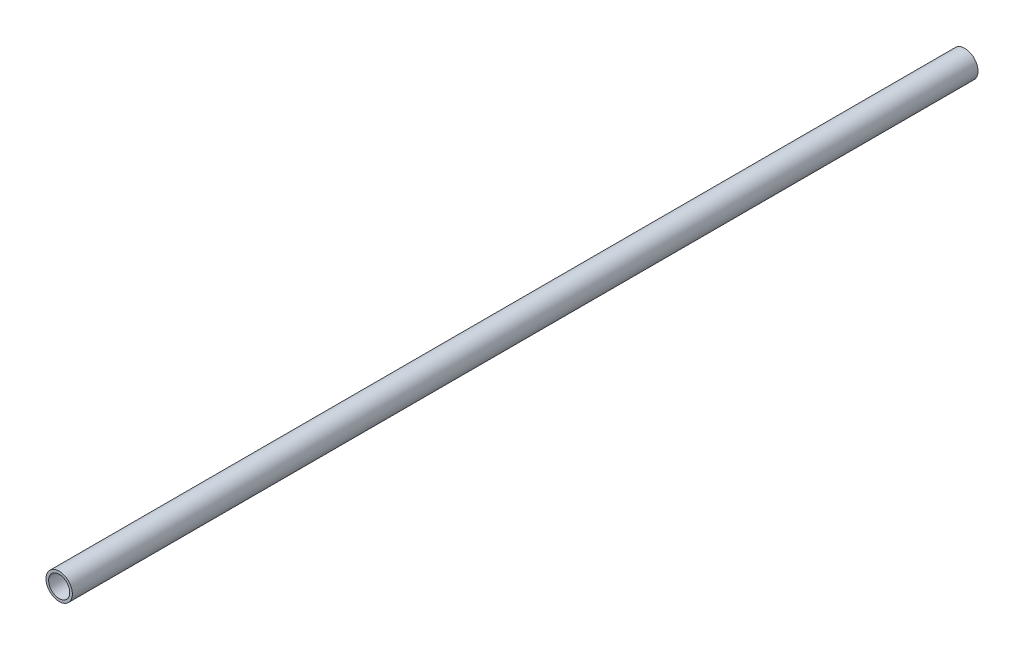
SolidWorks part; units mm, degrees
material "Aluminium 6060 T6"
ref_plane "Front Plane" through (0, 0, 0) normal (0, 0, 1) x (1, 0, 0)
ref_plane "Top Plane" through (0, 0, 0) normal (0, 1, 0) x (1, 0, 0)
ref_plane "Right Plane" through (0, 0, 0) normal (1, 0, 0) x (0, 0, -1)
sketch "Sketch1" plane through (0, 0, 0) normal (0, 0, 1) x (1, 0, 0)
  circle A0 centre (0, 0) radius 4
  dimension "D1" = 8
extrude "Extrude-Thin1" add sketch "Sketch1" along normal blind 343 thin thin type one direction wall 1
